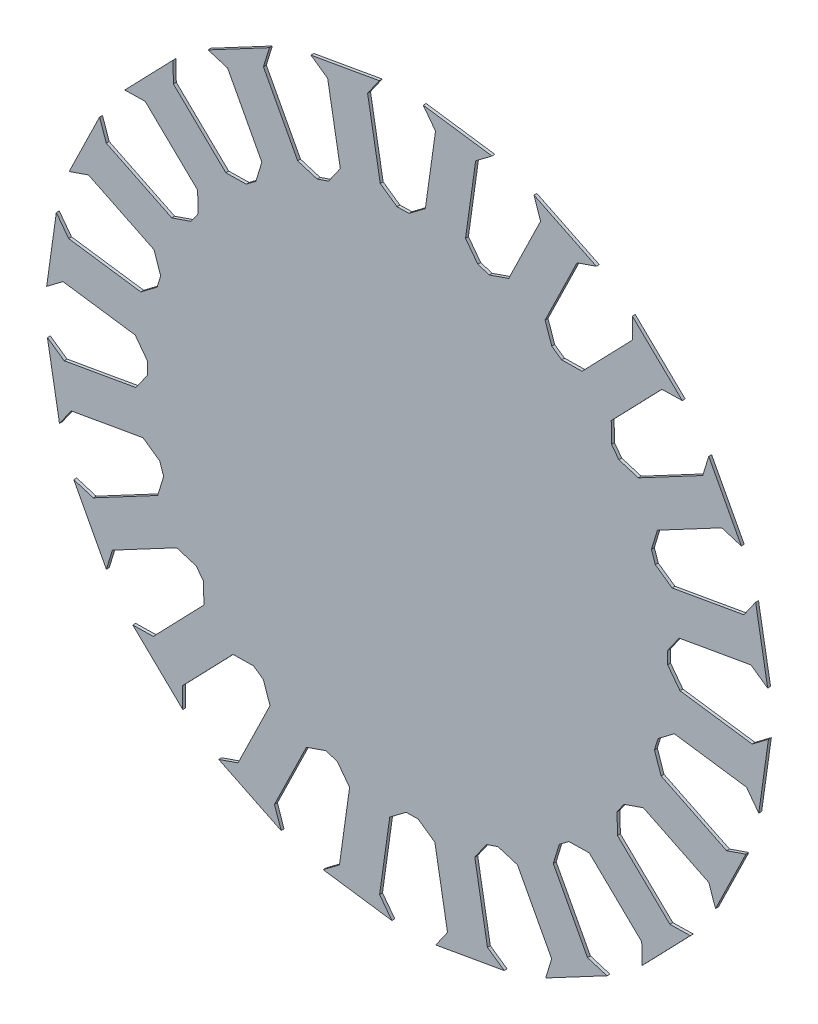
SolidWorks part; units mm, degrees
ref_plane "Ön Düzlem" through (0, 0, 0) normal (0, 0, 1) x (1, 0, 0)
ref_plane "Üst Düzlem" through (0, 0, 0) normal (0, 1, 0) x (1, 0, 0)
ref_plane "Sağ Düzlem" through (0, 0, 0) normal (1, 0, 0) x (0, 0, -1)
sketch "Çizim1" plane through (0, 0, 0) normal (0, 0, 1) x (1, 0, 0)
  line L0 (-3.656, 89.9257) -> (-1.5703, 89.9621)
  line L1 (-27.3209, 85.7529) -> (-29.2933, 85.0738)
  line L2 (-33.438, 120.4446) -> (-9.773, 124.6174)
  line L3 (-9.4482, 93.9815) -> (-13.8288, 118.8251)
  line L4 (-31.2656, 84.3947) -> (-29.2933, 85.0738)
  line L5 (-52.4829, 73.1133) -> (-54.1488, 71.8579)
  line L6 (-69.0208, 104.2167) -> (-47.8036, 115.4981)
  line L7 (-23.2651, 91.5452) -> (-27.6457, 116.3888)
  line L8 (-9.773, 124.6174) -> (-13.8288, 118.8251)
  line L9 (-33.438, 120.4446) -> (-27.6457, 116.3888)
  line L10 (-23.2651, 91.5452) -> (-27.3209, 85.7529)
  line L11 (-9.4482, 93.9815) -> (-3.656, 89.9257)
  line L12 (24.3115, 86.6542) -> (26.3064, 86.0443)
  line L13 (0.5154, 89.9985) -> (-1.5703, 89.9621)
  line L14 (5.418, 124.8825) -> (29.2142, 121.5382)
  line L15 (20.0561, 92.3014) -> (23.567, 117.2827)
  line L16 (6.1626, 94.254) -> (9.6735, 119.2353)
  line L17 (29.2142, 121.5382) -> (23.567, 117.2827)
  line L18 (5.418, 124.8825) -> (9.6735, 119.2353)
  line L19 (6.1626, 94.254) -> (0.5154, 89.9985)
  line L20 (20.0561, 92.3014) -> (24.3115, 86.6542)
  line L21 (49.8993, 74.9004) -> (51.608, 73.7039)
  line L22 (28.3012, 85.4344) -> (26.3064, 86.0443)
  line L23 (43.7437, 117.0961) -> (65.3417, 106.562)
  line L24 (47.5972, 81.5862) -> (58.6559, 104.2599)
  line L25 (34.9871, 87.7365) -> (46.0458, 110.4103)
  line L26 (65.3417, 106.562) -> (58.6559, 104.2599)
  line L27 (43.7437, 117.0961) -> (46.0458, 110.4103)
  line L28 (34.9871, 87.7365) -> (28.3012, 85.4344)
  line L29 (47.5972, 81.5862) -> (49.8993, 74.9004)
  line L30 (70.6025, 55.8147) -> (71.8579, 54.1488)
  line L31 (53.3168, 72.5074) -> (51.608, 73.7039)
  line L32 (77.7874, 97.8475) -> (95.0731, 81.1548)
  line L33 (70.4791, 62.8847) -> (88.0031, 81.0314)
  line L34 (60.3867, 72.6308) -> (77.9108, 90.7775)
  line L35 (95.0731, 81.1548) -> (88.0031, 81.0314)
  line L36 (77.7874, 97.8475) -> (77.9108, 90.7775)
  line L37 (60.3867, 72.6308) -> (53.3168, 72.5074)
  line L38 (70.4791, 62.8847) -> (70.6025, 55.8147)
  line L39 (84.3947, 31.2656) -> (85.0738, 29.2933)
  line L40 (73.1133, 52.4829) -> (71.8579, 54.1488)
  line L41 (104.2167, 69.0208) -> (115.4981, 47.8036)
  line L42 (86.4621, 38.0277) -> (108.736, 49.871)
  line L43 (79.8754, 50.4155) -> (102.1493, 62.2588)
  line L44 (115.4981, 47.8036) -> (108.736, 49.871)
  line L45 (104.2167, 69.0208) -> (102.1493, 62.2588)
  line L46 (79.8754, 50.4155) -> (73.1133, 52.4829)
  line L47 (86.4621, 38.0277) -> (84.3947, 31.2656)
  line L48 (89.9257, 3.656) -> (89.9621, 1.5703)
  line L49 (85.7529, 27.3209) -> (85.0738, 29.2933)
  line L50 (120.4446, 33.438) -> (124.6174, 9.773)
  line L51 (93.9815, 9.4482) -> (118.8251, 13.8288)
  line L52 (91.5452, 23.2651) -> (116.3888, 27.6457)
  line L53 (124.6174, 9.773) -> (118.8251, 13.8288)
  line L54 (120.4446, 33.438) -> (116.3888, 27.6457)
  line L55 (91.5452, 23.2651) -> (85.7529, 27.3209)
  line L56 (93.9815, 9.4482) -> (89.9257, 3.656)
  line L57 (86.6542, -24.3115) -> (86.0443, -26.3064)
  line L58 (89.9985, -0.5154) -> (89.9621, 1.5703)
  line L59 (124.8825, -5.418) -> (121.5382, -29.2142)
  line L60 (92.3014, -20.0561) -> (117.2827, -23.567)
  line L61 (94.254, -6.1626) -> (119.2353, -9.6735)
  line L62 (121.5382, -29.2142) -> (117.2827, -23.567)
  line L63 (124.8825, -5.418) -> (119.2353, -9.6735)
  line L64 (94.254, -6.1626) -> (89.9985, -0.5154)
  line L65 (92.3014, -20.0561) -> (86.6542, -24.3115)
  line L66 (74.9004, -49.8993) -> (73.7039, -51.608)
  line L67 (85.4344, -28.3012) -> (86.0443, -26.3064)
  line L68 (117.0961, -43.7437) -> (106.562, -65.3417)
  line L69 (81.5862, -47.5972) -> (104.2599, -58.6559)
  line L70 (87.7365, -34.9871) -> (110.4103, -46.0458)
  line L71 (106.562, -65.3417) -> (104.2599, -58.6559)
  line L72 (117.0961, -43.7437) -> (110.4103, -46.0458)
  line L73 (87.7365, -34.9871) -> (85.4344, -28.3012)
  line L74 (81.5862, -47.5972) -> (74.9004, -49.8993)
  line L75 (55.8147, -70.6025) -> (54.1488, -71.8579)
  line L76 (72.5074, -53.3168) -> (73.7039, -51.608)
  line L77 (97.8475, -77.7874) -> (81.1548, -95.0731)
  line L78 (62.8847, -70.4791) -> (81.0314, -88.0031)
  line L79 (72.6308, -60.3867) -> (90.7775, -77.9108)
  line L80 (-38.0277, 86.4621) -> (-49.871, 108.736)
  line L81 (81.1548, -95.0731) -> (81.0314, -88.0031)
  line L82 (-50.4155, 79.8754) -> (-62.2588, 102.1493)
  line L83 (97.8475, -77.7874) -> (90.7775, -77.9108)
  line L84 (-47.8036, 115.4981) -> (-49.871, 108.736)
  line L85 (-69.0208, 104.2167) -> (-62.2588, 102.1493)
  line L86 (-50.4155, 79.8754) -> (-52.4829, 73.1133)
  line L87 (-38.0277, 86.4621) -> (-31.2656, 84.3947)
  line L88 (72.6308, -60.3867) -> (72.5074, -53.3168)
  line L90 (-52.4829, 73.1133) -> (-69.0208, 104.2167) construction
  line L92 (-31.2656, 84.3947) -> (-47.8036, 115.4981) construction
  line L93 (-62.2588, 102.1493) -> (-49.871, 108.736) construction
  line L94 (-38.0277, 86.4621) -> (-50.4155, 79.8754) construction
  line L96 (-31.2656, 84.3947) -> (-52.4829, 73.1133) construction
  line L105 (62.8847, -70.4791) -> (55.8147, -70.6025)
  line L106 (31.2656, -84.3947) -> (29.2933, -85.0738)
  line L107 (52.4829, -73.1133) -> (54.1488, -71.8579)
  line L108 (69.0208, -104.2167) -> (47.8036, -115.4981)
  line L109 (38.0277, -86.4621) -> (49.871, -108.736)
  line L110 (50.4155, -79.8754) -> (62.2588, -102.1493)
  line L111 (47.8036, -115.4981) -> (49.871, -108.736)
  line L112 (69.0208, -104.2167) -> (62.2588, -102.1493)
  line L113 (50.4155, -79.8754) -> (52.4829, -73.1133)
  line L114 (38.0277, -86.4621) -> (31.2656, -84.3947)
  line L115 (3.656, -89.9257) -> (1.5703, -89.9621)
  line L116 (27.3209, -85.7529) -> (29.2933, -85.0738)
  line L117 (33.438, -120.4446) -> (9.773, -124.6174)
  line L118 (9.4482, -93.9815) -> (13.8288, -118.8251)
  line L119 (23.2651, -91.5452) -> (27.6457, -116.3888)
  line L120 (9.773, -124.6174) -> (13.8288, -118.8251)
  line L121 (33.438, -120.4446) -> (27.6457, -116.3888)
  line L122 (23.2651, -91.5452) -> (27.3209, -85.7529)
  line L123 (9.4482, -93.9815) -> (3.656, -89.9257)
  line L124 (-24.3115, -86.6542) -> (-26.3064, -86.0443)
  line L125 (-0.5154, -89.9985) -> (1.5703, -89.9621)
  line L126 (-5.418, -124.8825) -> (-29.2142, -121.5382)
  line L127 (-20.0561, -92.3014) -> (-23.567, -117.2827)
  line L128 (-6.1626, -94.254) -> (-9.6735, -119.2353)
  line L129 (-29.2142, -121.5382) -> (-23.567, -117.2827)
  line L130 (-5.418, -124.8825) -> (-9.6735, -119.2353)
  line L131 (-6.1626, -94.254) -> (-0.5154, -89.9985)
  line L132 (-20.0561, -92.3014) -> (-24.3115, -86.6542)
  line L133 (-49.8993, -74.9004) -> (-51.608, -73.7039)
  line L134 (-28.3012, -85.4344) -> (-26.3064, -86.0443)
  line L135 (-43.7437, -117.0961) -> (-65.3417, -106.562)
  line L136 (-47.5972, -81.5862) -> (-58.6559, -104.2599)
  line L137 (-34.9871, -87.7365) -> (-46.0458, -110.4103)
  line L138 (-65.3417, -106.562) -> (-58.6559, -104.2599)
  line L139 (-43.7437, -117.0961) -> (-46.0458, -110.4103)
  line L140 (-34.9871, -87.7365) -> (-28.3012, -85.4344)
  line L141 (-47.5972, -81.5862) -> (-49.8993, -74.9004)
  line L142 (-70.6025, -55.8147) -> (-71.8579, -54.1488)
  line L143 (-53.3168, -72.5074) -> (-51.608, -73.7039)
  line L144 (-77.7874, -97.8475) -> (-95.0731, -81.1548)
  line L145 (-70.4791, -62.8847) -> (-88.0031, -81.0314)
  line L146 (-60.3867, -72.6308) -> (-77.9108, -90.7775)
  line L147 (-95.0731, -81.1548) -> (-88.0031, -81.0314)
  line L148 (-77.7874, -97.8475) -> (-77.9108, -90.7775)
  line L149 (-60.3867, -72.6308) -> (-53.3168, -72.5074)
  line L150 (-70.4791, -62.8847) -> (-70.6025, -55.8147)
  line L151 (-84.3947, -31.2656) -> (-85.0738, -29.2933)
  line L152 (-73.1133, -52.4829) -> (-71.8579, -54.1488)
  line L153 (-104.2167, -69.0208) -> (-115.4981, -47.8036)
  line L154 (-86.4621, -38.0277) -> (-108.736, -49.871)
  line L155 (-79.8754, -50.4155) -> (-102.1493, -62.2588)
  line L156 (-115.4981, -47.8036) -> (-108.736, -49.871)
  line L157 (-104.2167, -69.0208) -> (-102.1493, -62.2588)
  line L158 (-79.8754, -50.4155) -> (-73.1133, -52.4829)
  line L159 (-86.4621, -38.0277) -> (-84.3947, -31.2656)
  line L160 (-89.9257, -3.656) -> (-89.9621, -1.5703)
  line L161 (-85.7529, -27.3209) -> (-85.0738, -29.2933)
  line L162 (-120.4446, -33.438) -> (-124.6174, -9.773)
  line L163 (-93.9815, -9.4482) -> (-118.8251, -13.8288)
  line L164 (-91.5452, -23.2651) -> (-116.3888, -27.6457)
  line L165 (-124.6174, -9.773) -> (-118.8251, -13.8288)
  line L166 (-120.4446, -33.438) -> (-116.3888, -27.6457)
  line L167 (-91.5452, -23.2651) -> (-85.7529, -27.3209)
  line L168 (-93.9815, -9.4482) -> (-89.9257, -3.656)
  line L169 (-86.6542, 24.3115) -> (-86.0443, 26.3064)
  line L170 (-89.9985, 0.5154) -> (-89.9621, -1.5703)
  line L171 (-124.8825, 5.418) -> (-121.5382, 29.2142)
  line L172 (-92.3014, 20.0561) -> (-117.2827, 23.567)
  line L173 (-94.254, 6.1626) -> (-119.2353, 9.6735)
  line L174 (-121.5382, 29.2142) -> (-117.2827, 23.567)
  line L175 (-124.8825, 5.418) -> (-119.2353, 9.6735)
  line L176 (-94.254, 6.1626) -> (-89.9985, 0.5154)
  line L177 (-92.3014, 20.0561) -> (-86.6542, 24.3115)
  line L178 (-74.9004, 49.8993) -> (-73.7039, 51.608)
  line L179 (-85.4344, 28.3012) -> (-86.0443, 26.3064)
  line L180 (-117.0961, 43.7437) -> (-106.562, 65.3417)
  line L181 (-81.5862, 47.5972) -> (-104.2599, 58.6559)
  line L182 (-87.7365, 34.9871) -> (-110.4103, 46.0458)
  line L183 (-106.562, 65.3417) -> (-104.2599, 58.6559)
  line L184 (-117.0961, 43.7437) -> (-110.4103, 46.0458)
  line L185 (-87.7365, 34.9871) -> (-85.4344, 28.3012)
  line L186 (-81.5862, 47.5972) -> (-74.9004, 49.8993)
  line L187 (-55.8147, 70.6025) -> (-54.1488, 71.8579)
  line L188 (-72.5074, 53.3168) -> (-73.7039, 51.608)
  line L189 (-97.8475, 77.7874) -> (-81.1548, 95.0731)
  line L190 (-62.8847, 70.4791) -> (-81.0314, 88.0031)
  line L191 (-72.6308, 60.3867) -> (-90.7775, 77.9108)
  line L192 (-81.1548, 95.0731) -> (-81.0314, 88.0031)
  line L193 (-97.8475, 77.7874) -> (-90.7775, 77.9108)
  line L194 (-72.6308, 60.3867) -> (-72.5074, 53.3168)
  line L195 (-62.8847, 70.4791) -> (-55.8147, 70.6025)
  point P82 (0, 0)
  point P226 (0, 0)
  dimension "D1" = 20
  dimension "D2" = 5
extrude "Yükseklik-Ekstrüzyon1" add sketch "Çizim1" along normal blind 1
